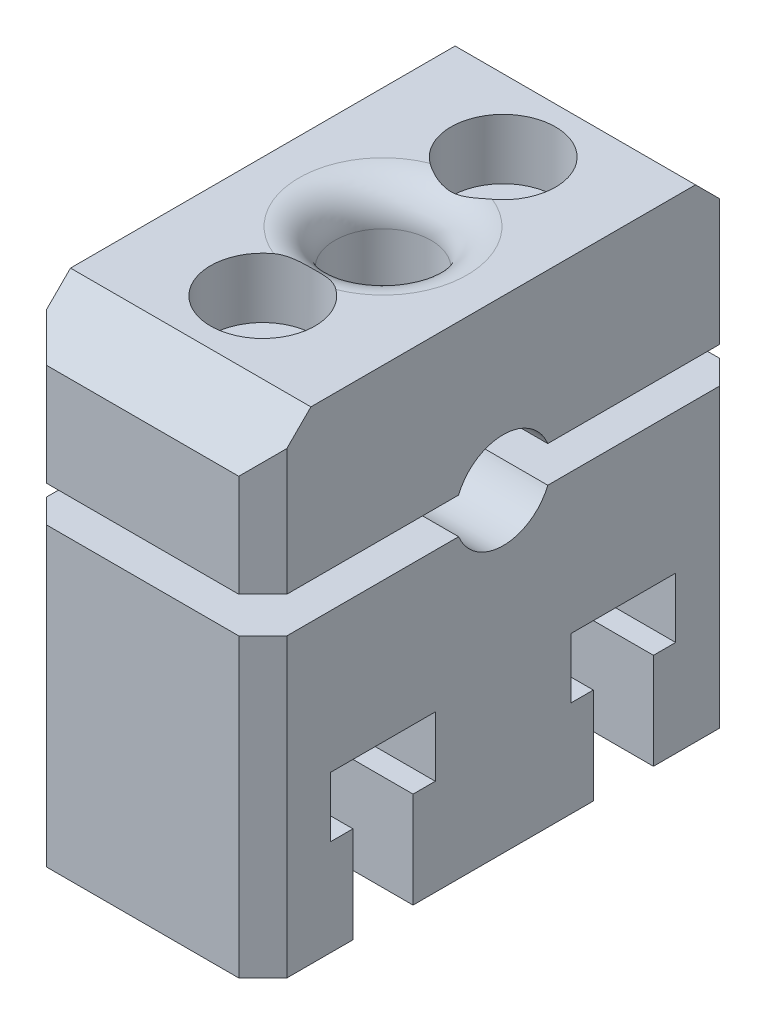
SolidWorks part; units mm, degrees
ref_plane "정면" through (0, 0, 0) normal (0, 0, 1) x (1, 0, 0)
ref_plane "윗면" through (0, 0, 0) normal (0, 1, 0) x (1, 0, 0)
ref_plane "우측면" through (0, 0, 0) normal (1, 0, 0) x (0, 0, -1)
sketch "스케치1" plane through (0, 0, 0) normal (1, 0, 0) x (0, 0, -1)
  line L0 (-20, 14) -> (20, 14)
  line L1 (-20, -26.15) -> (20, -26.15)
  line L2 (-20, -26.15) -> (-20, 14)
  line L4 (20, -26.15) -> (20, 14)
  line L5 (0, 14) -> (0, -26.15) construction
  circle A0 centre (0, 0) radius 4
  dimension "D1" = 8
  dimension "D2" = 40
  dimension "D3" = 26.15
  dimension "D4" = 14
extrude "보스-돌출1" add sketch "스케치1" along normal blind 20
sketch "스케치2" plane through (0, 14, 0) normal (0, 1, 0) x (1, 0, 0)
  line L0 (0, 0) -> (20, 0) construction
  line L1 (0, 20) -> (0, -20) construction
  line L2 (20, 20) -> (20, -20) construction
  circle A0 centre (10, 0) radius 4
  dimension "D1" = 8
extrude "컷-돌출1" cut sketch "스케치2" against normal blind 14
sketch "스케치3" plane through (0, 14, 0) normal (0, 1, 0) x (1, 0, 0)
  line L0 (10, 20) -> (10, 0) construction
  line L1 (20, 20) -> (0, 20) construction
  line L2 (10, 0) -> (0, 0) construction
  circle A1 centre (10, 10) radius 2.5
  circle A2 centre (10, -10) radius 2.5
  circle A3 centre (10, 10) radius 4.35
  circle A4 centre (10, -10) radius 4.35
  circle A5 centre (10, 10) radius 2.35
  circle A6 centre (10, -10) radius 2.35
  dimension "D1" = 5
  dimension "D3" = 8.7
  dimension "D4" = 4.7
  dimension "D2" = 10
extrude "컷-돌출3" cut sketch "스케치3" along normal blind 8 from surface contours A1 | A2 starting at face at (10, -26.15, 0)
sketch "스케치5" plane through (0, -26.15, 0) normal (0, -1, 0) x (1, 0, 0)
  line L0 (0, 0) -> (20, 0) construction
  line L1 (20, 20) -> (20, -20) construction
  circle A0 centre (10, 10) radius 4.35
  circle A1 centre (10, -10) radius 4.35
  dimension "D1" = 8.7
extrude "컷-돌출4" cut sketch "스케치5" against normal blind 5 from offset 8 offset against normal yes
sketch "스케치6" plane through (0, 0, 0) normal (-1, 0, 0) x (0, 0, 1)
  line L0 (20, 14) -> (20, -26.15) construction
  line L1 (-20, -1.5) -> (20, -1.5)
  line L2 (-20, -1.5) -> (-20, 1.5)
  line L3 (-20, 1.5) -> (20, 1.5)
  line L4 (20, -1.5) -> (20, 1.5)
  line L5 (-20, -1.5) -> (20, 1.5) construction
  line L6 (-20, 1.5) -> (20, -1.5) construction
  point P0 (0, 0)
  dimension "D1" = 3
extrude "컷-돌출6" cut sketch "스케치6" against normal through all
extrude "컷-돌출5" cut sketch "스케치3<6>" against normal through all from surface contours A5 | A6 starting at face at (10, -1.5, 11.854)
sketch "스케치3<6>" plane through (0, 14, 0) normal (0, 1, 0) x (1, 0, 0) same geometry as "스케치3"
sketch "스케치7" plane through (20, 0, 0) normal (1, 0, 0) x (0, 0, -1)
  line L0 (0, 0) -> (0, -26.15) construction
  line L1 (-20, -26.15) -> (20, -26.15) construction
  line L2 (14.35, -13.15) -> (14.35, -18.15)
  line L3 (-14.35, -13.15) -> (-5.65, -13.15)
  line L4 (-14.35, -13.15) -> (-14.35, -18.15)
  line L5 (-14.35, -18.15) -> (-5.65, -18.15)
  line L6 (-5.65, -13.15) -> (-5.65, -18.15)
  line L7 (14.35, -13.15) -> (5.65, -13.15)
  line L8 (5.65, -13.15) -> (5.65, -18.15)
  line L9 (14.35, -18.15) -> (5.65, -18.15)
  line L10 (-10, -18.15) -> (-10, -26.15) construction
  line L11 (10, -18.15) -> (10, -26.15) construction
  line L12 (-7.5, -18.15) -> (-7.5, -26.15)
  line L13 (7.5, -18.15) -> (7.5, -26.15)
  line L14 (-12.5, -18.15) -> (-12.5, -26.15)
  line L15 (12.5, -18.15) -> (12.5, -26.15)
  line L16 (-7.5, -26.15) -> (-12.5, -26.15)
  line L17 (7.5, -26.15) -> (12.5, -26.15)
  line L18 (-20, -1.5) -> (-20, -26.15) construction
  line M17 (-20, -26.15) -> (20, -26.15)
  dimension "D1" = 8.7
  dimension "D2" = 10
  dimension "D3" = 2.5
  dimension "D4" = 5
  dimension "D5" = 8
extrude "컷-돌출7" cut sketch "스케치7" against normal blind 10 contours L6 L3 L4 L5 | L5 L14 L12 M17 | L9 L2 L7 L8 | L15 L9 L13 M17 | L2 L7 L8 L9 region at (20, -22.15, 10) region at (20, -15.65, -10) region at (20, -22.15, -10) region at (20, -15.65, 10)
extrude "컷-돌출8" cut sketch "스케치3<7>" against normal blind 5 contours A4 | A3
sketch "스케치3<7>" plane through (0, 14, 0) normal (0, 1, 0) x (1, 0, 0) same geometry as "스케치3"
extrude "컷-돌출9" cut sketch "스케치3<8>" against normal blind 24 contours A2 | A1
sketch "스케치3<8>" plane through (0, 14, 0) normal (0, 1, 0) x (1, 0, 0) same geometry as "스케치3"
ref_plane "평면3" through (0, -10, 0) normal (0, 1, 0) x (1, 0, 0)
sketch "스케치8" plane through (0, -10, 0) normal (0, 1, 0) x (1, 0, 0)
  line L0 (0, 0) -> (20, 0) construction
  line L1 (14, -7.6906) -> (10, -5.3812)
  line L2 (10, -5.3812) -> (6, -7.6906)
  line L3 (6, -7.6906) -> (6, -12.3094)
  line L4 (6, -12.3094) -> (10, -14.6188)
  line L5 (10, -14.6188) -> (14, -12.3094)
  line L6 (14, -12.3094) -> (14, -7.6906)
  line L7 (20, -7.5) -> (20, 7.5) construction
  line L8 (14, 12.3094) -> (14, 7.6906)
  line L9 (10, 14.6188) -> (14, 12.3094)
  line L10 (6, 12.3094) -> (10, 14.6188)
  line L11 (6, 7.6906) -> (6, 12.3094)
  line L12 (10, 5.3812) -> (6, 7.6906)
  line L13 (14, 7.6906) -> (10, 5.3812)
  circle A0 centre (10, -10) radius 2.35 construction
  circle A1 centre (10, -10) radius 2.35
  circle A2 centre (10, 10) radius 2.35 construction
  circle A3 centre (10, 10) radius 2.35
  circle A4 centre (10, -10) radius 4 construction
  circle A5 centre (10, 10) radius 4 construction
  dimension "D1" = 8
extrude "컷-돌출10" cut sketch "스케치8" along normal blind 4 contours A1 | L5 L6 L1 L2 L3 L4 A1 | L13 L8 L9 L10 L11 L12 A3 | A3 region at (13.8778, -10, 10) region at (13.8778, -10, -10) region at (10, -10, 10) region at (10, -10, -10)
fillet "필렛1" radius 3 1 edges at (10, 14, 4)
chamfer "모따기2" distance 4 angle 45 2 edges at (10, 14, -20) (10, 14, 20)
chamfer "모따기3" distance 2 angle 45 4 edges at (0, -13.825, -20) (20, -13.825, -20) (20, -13.825, 20) (0, -13.825, 20)
chamfer "모따기4" distance 2 angle 45 4 edges at (0, 5.75, 20) (20, 5.75, 20) (0, 5.75, -20) (20, 5.75, -20)
